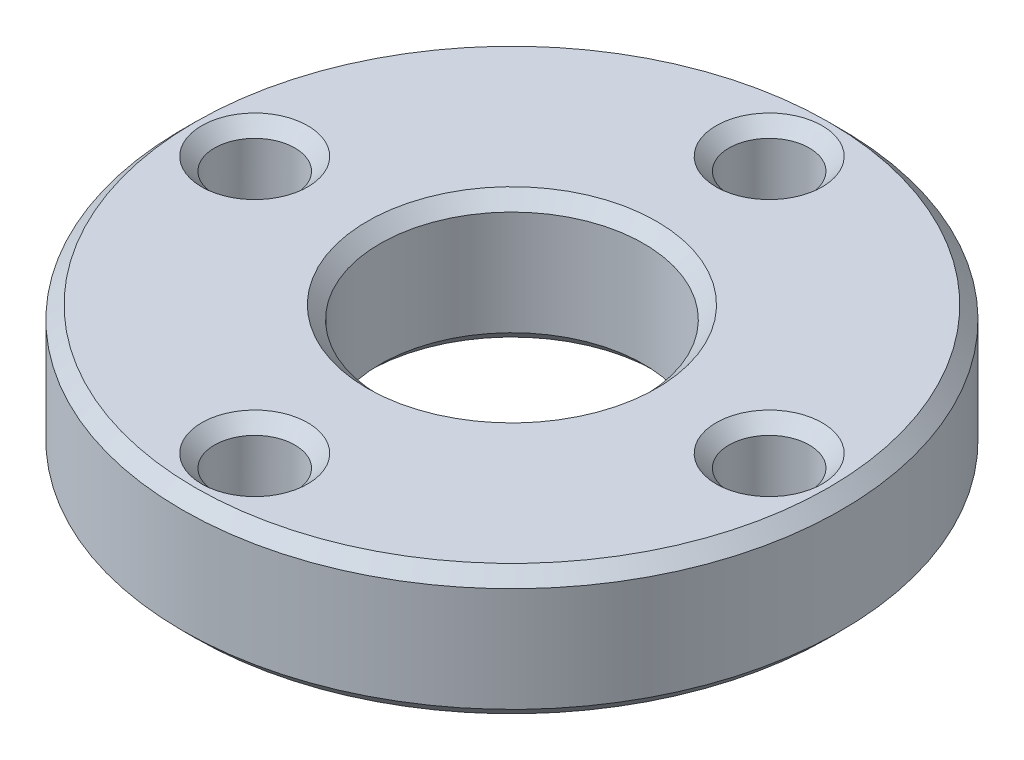
SolidWorks part; units mm, degrees
material "ABS"
ref_plane "Front Plane" through (0, 0, 0) normal (0, 0, 1) x (1, 0, 0)
ref_plane "Top Plane" through (0, 0, 0) normal (0, 1, 0) x (1, 0, 0)
ref_plane "Right Plane" through (0, 0, 0) normal (1, 0, 0) x (0, 0, -1)
sketch "Sketch1" plane through (0, 0, 0) normal (0, 1, 0) x (1, 0, 0)
  circle A0 centre (0, 0) radius 10.25
  circle A1 centre (0, 0) radius 4.1
  dimension "D1" = 20.5
  dimension "D2" = 8.2
extrude "Boss-Extrude1" add sketch "Sketch1" against normal blind 4.05
sketch "Sketch4" plane through (0, 0, 0) normal (0, 1, 0) x (1, 0, 0)
  circle A0 centre (0, 0) radius 8 construction
  circle A1 centre (0, 8) radius 1.25
  dimension "D1" = 16
  dimension "D2" = 2.5
extrude "Cut-Extrude1" cut sketch "Sketch4" against normal through all
pattern_circular "CirPattern1" count 4 over 360 about axis through (0, 0, 0) along (0, 1, 0) of "Cut-Extrude1"
chamfer "Chamfer1" distance 0.4 angle 45 12 edges at (0, -4.05, 6.75) (6.75, -4.05, 0) (0, -4.05, -6.75) (-6.75, -4.05, 0) (0, -4.05, 4.1) (6.75, 0, 0) (0, 0, 6.75) (0, -4.05, 10.25) (-6.75, 0, 0) (0, 0, 10.25) (0, 0, -6.75) (0, 0, 4.1)
